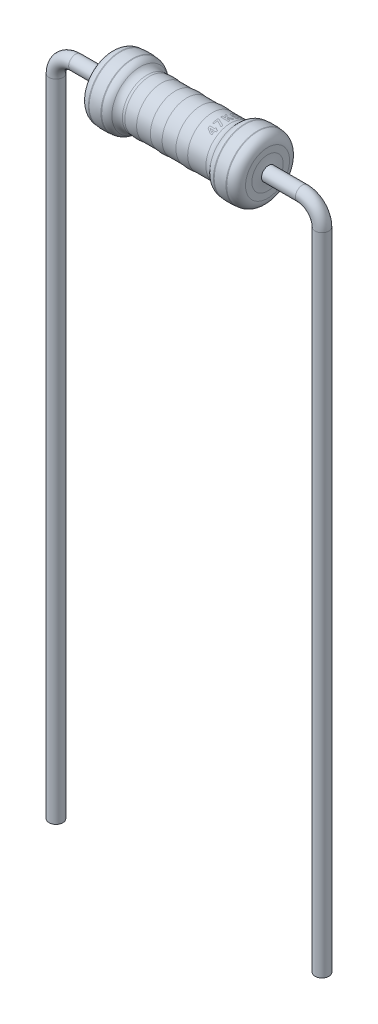
SolidWorks part; units mm, degrees
material "Plain Carbon Steel"
ref_plane "Front Plane" through (0, 0, 0) normal (0, 0, 1) x (1, 0, 0)
ref_plane "Top Plane" through (0, 0, 0) normal (0, 1, 0) x (1, 0, 0)
ref_plane "Right Plane" through (0, 0, 0) normal (1, 0, 0) x (0, 0, -1)
sketch "Sketch1" plane through (0, 0, 0) normal (0, 0, 1) x (1, 0, 0)
  line L0 (-4.33, 0) -> (4.33, 0)
  line L1 (-5.08, -0.75) -> (-5.08, -25.4)
  line L2 (5.08, -0.75) -> (5.08, -25.4)
  line L3 (-5.08, -25.4) -> (5.08, -25.4) construction
  line L4 (0, 0) -> (0, -25.4) construction
  arc A0 (-4.33, 0) -> (-5.08, -0.75) centre (-4.33, -0.75) ccw
  arc A1 (4.33, 0) -> (5.08, -0.75) centre (4.33, -0.75) cw
  dimension "D2" = 0.75
  dimension "D1" = 10.16
  dimension "D3" = 25.4
ref_plane "Plane1" through (-5.08, -25.4, 0) normal (0, -1, 0) x (-1, 0, 0)
sketch "Sketch2" plane through (-5.08, -25.4, 0) normal (0, -1, 0) x (-1, 0, 0)
  circle A0 centre (0, 0) radius 0.265
  dimension "D1" = 0.53
sweep "Sweep1" add profiles "Sketch2" path "Sketch1"
sketch "Sketch3" plane through (0, 0, 0) normal (0, 0, 1) x (1, 0, 0)
  line L0 (-3, 0) -> (3, 0)
  line L5 (-3, 0) -> (-3, 1.2)
  line L6 (3, 0) -> (3, 1.2)
  line L7 (-3, 1.2) -> (-1.8, 1.2)
  line L8 (3, 1.2) -> (1.8, 1.2)
  line L9 (-1.8, 1.2) -> (-1.8, 0.95)
  line L10 (-1.8, 0.95) -> (1.8, 0.95)
  line L11 (1.8, 0.95) -> (1.8, 1.2)
  line L12 (0, 0) -> (0, 0.95) construction
  dimension "D1" = 6
  dimension "D2" = 1.2
  dimension "D3" = 3.6
  dimension "D4" = 0.95
  dimension "D5" = 0.25
revolve "Revolve1" add sketch "Sketch3" angle 360 about L0
fillet "Fillet-1" radius 0.35 2 edges at (1.8, 0, 1.2) (-1.8, 0, 1.2)
fillet "Fillet-2" radius 0.36 4 edges at (3, 0, 1.2) (-3, 0, 1.2) (1.8, 0, 0.95) (-1.8, 0, 0.95)
sketch "Sketch5" plane through (0, 0, 0) normal (0, 0, 1) x (1, 0, 0)
  line L0 (-2.64, -1.2) -> (-2.1354, -1.2) construction
  line L5 (-2.3877, -1.2) -> (-2.3877, 0) construction
  line L10 (-3, 1.2) -> (-1.8, 1.2) construction
  line L15 (-1.05, 0.95) -> (-0.525, 0.95) construction
  line L16 (-3, 0) -> (3, 0) construction
  line L17 (-2.6127, 1.2) -> (-2.1627, 1.2) construction
  line L18 (-2.6127, 1.2) -> (-2.6127, 0) construction
  line L19 (-2.6127, 0) -> (-2.1627, 0) construction
  line L20 (-2.1627, 1.2) -> (-2.1627, 0) construction
  line L21 (-1.8, 0.95) -> (1.8, 0.95) construction
  line L22 (2.6127, 1.2) -> (2.1627, 1.2) construction
  line L23 (2.6127, 1.2) -> (2.6127, 0) construction
  line L24 (2.6127, 0) -> (2.1627, 0) construction
  line L25 (2.1627, 1.2) -> (2.1627, 0) construction
  line L26 (-1.05, 0.95) -> (-1.5, 0.95) construction
  line L27 (-1.05, 0.95) -> (-1.05, 0) construction
  line L28 (-1.05, 0) -> (-1.5, 0) construction
  line L29 (-1.5, 0.95) -> (-1.5, 0) construction
  line L30 (-2.3877, 1.2) -> (-2.3877, 1.22) construction
  line L31 (-0.075, 0.95) -> (-0.525, 0.95) construction
  line L32 (-0.075, 0.95) -> (-0.075, 0) construction
  line L33 (-0.075, 0) -> (-0.525, 0) construction
  line L34 (-0.525, 0.95) -> (-0.525, 0) construction
  line L35 (-1.275, 0.95) -> (-1.275, 0.97) construction
  line L36 (-0.3, 0.95) -> (-0.3, 0.97) construction
  line L37 (2.3877, 1.2) -> (2.3877, 1.22) construction
  line L39 (2.1354, -1.2) -> (2.64, -1.2) construction
  line L41 (2.3877, -1.2) -> (2.3877, 0) construction
  line L44 (3, 1.2) -> (1.8, 1.2) construction
  line L46 (-0.075, 0.95) -> (0.45, 0.95) construction
  line L48 (-3, 0) -> (-3, 0.6)
  line L49 (-3, 0) -> (-3, 1.2) construction
  line L50 (-3, 0) -> (-3.05, 0)
  line L51 (-3.05, 0) -> (-3.05, 0.2)
  line L52 (3, 0) -> (3.05, 0)
  line L53 (3.05, 0) -> (3.05, 0.2)
  line L54 (3, 0) -> (3, 0.6)
  line L55 (3, 0) -> (3, 1.2) construction
  line L56 (-1.05, 0) -> (-0.525, 0) construction
  line L58 (-0.075, 0) -> (0.45, 0) construction
  line L59 (0.45, 0) -> (0.45, 0.95) construction
  line L60 (0.45, 0) -> (0.9, 0) construction
  line L61 (0.9, 0) -> (0.9, 0.95) construction
  line L62 (1.5946, 0.95) -> (-1.5946, 0.95) construction
  line L63 (0.9, 0.95) -> (0.45, 0.95) construction
  line L64 (0.675, 0.95) -> (0.675, 0.97) construction
  arc A0 (-2.6127, 1.2) -> (-2.1627, 1.2) centre (-2.3877, -0.0556) cw construction
  arc A1 (-1.5, 0.95) -> (-1.05, 0.95) centre (-1.275, -0.3056) cw construction
  arc A2 (-0.525, 0.95) -> (-0.075, 0.95) centre (-0.3, -0.3056) cw construction
  arc A3 (2.1627, 1.2) -> (2.6127, 1.2) centre (2.3877, -0.0556) cw construction
  arc A6 (-3, 0.6) -> (-3.05, 0.2) centre (-4.625, 0.6) cw
  arc A7 (3.05, 0.2) -> (3, 0.6) centre (4.625, 0.6) cw
  arc A8 (0.45, 0.95) -> (0.9, 0.95) centre (0.675, -0.3056) cw construction
  dimension "D4" = 0.02
  dimension "D5" = 0.05
  dimension "D7" = 0.6
  dimension "D2" = 1.5
  dimension "D3" = 2.4
  dimension "D1" = 0.45
  dimension "D6" = 0.2
revolve "Revolve Ends" add sketch "Sketch5" angle 360 about L19
sketch "Sketch12" plane through (0, 0, 0) normal (0, 0, 1) x (1, 0, 0)
  line L0 (-2.6127, 0) -> (-2.1627, 0) construction
  line L1 (-2.6127, 0) -> (-2.1627, 0)
  line L2 (-2.6127, 1.2) -> (-2.6127, 0) construction
  line L3 (-2.6127, 1.2) -> (-2.6127, 0)
  line L4 (-2.1627, 1.2) -> (-2.1627, 0) construction
  line L5 (-2.1627, 1.2) -> (-2.1627, 0)
  arc A0 (-2.1627, 1.2) -> (-2.6127, 1.2) centre (-2.3877, -0.0556) ccw construction
  arc A1 (-2.1627, 1.2) -> (-2.6127, 1.2) centre (-2.3877, -0.0556) ccw
revolve "Revolve BAND 1" add sketch "Sketch12" angle 360 about L19
sketch "Sketch7" plane through (0, 0, 0) normal (0, 0, 1) x (1, 0, 0)
  line L0 (-1.05, 0) -> (-1.5, 0) construction
  line L1 (-1.05, 0.95) -> (-1.05, 0) construction
  line L2 (-1.5, 0.95) -> (-1.5, 0) construction
  line L3 (-1.05, 0.95) -> (-1.05, 0)
  line L4 (-1.5, 0.95) -> (-1.5, 0)
  line L5 (-1.05, 0) -> (-1.5, 0)
  arc A0 (-1.05, 0.95) -> (-1.5, 0.95) centre (-1.275, -0.3056) ccw construction
  arc A1 (-1.05, 0.95) -> (-1.5, 0.95) centre (-1.275, -0.3056) ccw
revolve "Revolve BAND 2" add sketch "Sketch7" angle 360 about L28
sketch "Sketch8" plane through (0, 0, 0) normal (0, 0, 1) x (1, 0, 0)
  line L0 (-0.075, 0.95) -> (-0.075, 0) construction
  line L1 (-0.075, 0) -> (-0.525, 0) construction
  line L2 (-0.525, 0.95) -> (-0.525, 0) construction
  line L3 (-0.075, 0.95) -> (-0.075, 0)
  line L4 (-0.075, 0) -> (-0.525, 0)
  line L5 (-0.525, 0.95) -> (-0.525, 0)
  arc A0 (-0.075, 0.95) -> (-0.525, 0.95) centre (-0.3, -0.3056) ccw construction
  arc A1 (-0.075, 0.95) -> (-0.525, 0.95) centre (-0.3, -0.3056) ccw
revolve "Revolve BAND 3" add sketch "Sketch8" angle 360 about L33
sketch "Sketch9" plane through (0, 0, 0) normal (0, 0, 1) x (1, 0, 0)
  line L0 (0.9, 0) -> (0.9, 0.95) construction
  line L1 (0.45, 0) -> (0.45, 0.95) construction
  line L2 (0.45, 0) -> (0.9, 0) construction
  line L3 (0.9, 0) -> (0.9, 0.95)
  line L4 (0.45, 0) -> (0.45, 0.95)
  line L5 (0.45, 0) -> (0.9, 0)
  arc A0 (0.9, 0.95) -> (0.45, 0.95) centre (0.675, -0.3056) ccw construction
  arc A1 (0.9, 0.95) -> (0.45, 0.95) centre (0.675, -0.3056) ccw
revolve "Revolve BAND 4" add sketch "Sketch9" angle 360 about L60
sketch "Sketch11" plane through (0, 0, 0) normal (0, 0, 1) x (1, 0, 0)
  line L0 (2.6127, 1.2) -> (2.6127, 0) construction
  line L1 (2.1627, 1.2) -> (2.1627, 0) construction
  line L2 (2.6127, 0) -> (2.1627, 0) construction
  line L3 (2.6127, 1.2) -> (2.6127, 0)
  line L4 (2.1627, 1.2) -> (2.1627, 0)
  line L5 (2.6127, 0) -> (2.1627, 0)
  arc A0 (2.6127, 1.2) -> (2.1627, 1.2) centre (2.3877, -0.0556) ccw construction
  arc A1 (2.6127, 1.2) -> (2.1627, 1.2) centre (2.3877, -0.0556) ccw
revolve "Revolve5" add sketch "Sketch11" angle 360 about L24
ref_plane "Plane2" through (0, 2, 0) normal (0, 1, 0) x (1, 0, 0)
sketch "Sketch6" plane through (0, 2, 0) normal (0, 1, 0) x (1, 0, 0)
  line L0 (0, 0) -> (1.5, 0) construction
  line L1 (1.5, 1) -> (1.5, -1) construction
  text T0 "47KΩ" font "Calibri" height 0.3
  dimension "D1" = 1.5
  dimension "D2" = 2
wrap "Wrap1" sketch "Sketch6" wrap type scribe source sketch "Sketch6" face at (1.5946, 0, 0.95)
